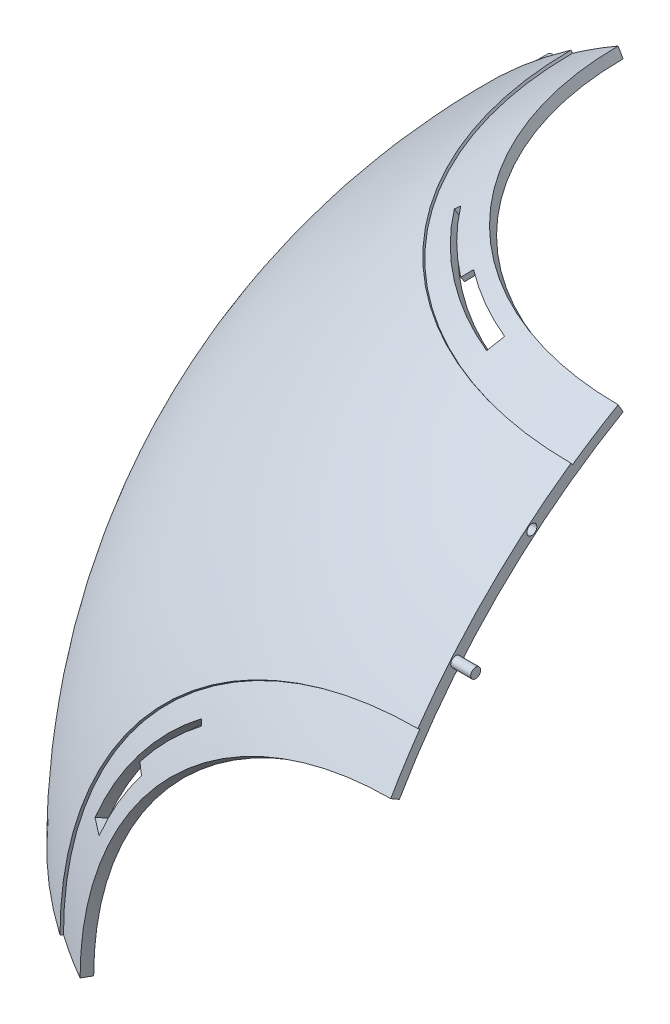
SolidWorks part; units mm, degrees
ref_plane "Front Plane" through (0, 0, 0) normal (0, 0, 1) x (1, 0, 0)
ref_plane "Top Plane" through (0, 0, 0) normal (0, 1, 0) x (1, 0, 0)
ref_plane "Right Plane" through (0, 0, 0) normal (1, 0, 0) x (0, 0, -1)
sketch "Sketch1" plane through (0, 0, 0) normal (0, 0, 1) x (1, 0, 0)
  line L0 (0, 0) -> (0, 282.4311)
  line L1 (-122.5, 212.1762) -> (-124.5, 215.6403)
  line L2 (-142.8205, 203.9689) -> (-143.3941, 204.788)
  line L3 (-245, 0) -> (-250, 0)
  arc A0 (-143.3941, 204.788) -> (-250, 0) centre (0, 0) ccw
  arc A1 (-124.5, 215.6403) -> (-142.8205, 203.9689) centre (0, 0) ccw
  arc A2 (-122.5, 212.1762) -> (-245, 0) centre (0, 0) ccw
  dimension "D1" = 500
  dimension "D2" = 498
  dimension "D3" = 490
  dimension "D4" = 5
  dimension "D5" = 30
revolve "Revolve1" add sketch "Sketch1" angle 90 about L0 region at (-214.3457, 123.7526, 0)
sketch "Sketch2" plane through (0, 0, 0) normal (1, 0, 0) x (0, 0, -1)
  line L0 (0, 0) -> (-288.7114, 0)
  line L1 (-212.1762, 122.5) -> (-215.6403, 124.5)
  line L2 (-203.9689, 142.8205) -> (-204.788, 143.3941)
  arc A0 (-204.788, 143.3941) -> (-250, 0) centre (0, 0) ccw
  arc A1 (-212.1762, 122.5) -> (-245, 0) centre (0, 0) ccw
  arc A2 (-203.9689, 142.8205) -> (-215.6403, 124.5) centre (0, 0) ccw
  dimension "D1" = 498
  dimension "D2" = 490
  dimension "D3" = 5
  dimension "D4" = 30
revolve "Cut-Revolve2" cut sketch "Sketch2" angle 360 about L0 region at (0, 1.506, 247.5)
sketch "Sketch3" plane through (0, 0, 0) normal (0, 0, -1) x (-1, 0, 0)
  line L0 (0, 0) -> (307.3195, 0)
  line L1 (203.9689, 142.8205) -> (204.788, 143.3941)
  line L2 (0, 0) -> (215.6403, 124.5)
  arc A0 (245, 0) -> (212.1762, 122.5) centre (0, 0) ccw
  arc A1 (250, 0) -> (204.788, 143.3941) centre (0, 0) ccw
  arc A2 (215.6403, 124.5) -> (203.9689, 142.8205) centre (0, 0) ccw
  dimension "D1" = 498
  dimension "D2" = 30
  dimension "D3" = 5
revolve "Cut-Revolve3" cut sketch "Sketch3" angle 360 about L0 region at (-238.1065, 63.8005, 0)
sketch "Sketch4" plane through (0, 0, 0) normal (0, 0, -1) x (-1, 0, 0)
  line L0 (0, 0) -> (143.3941, 204.788)
  circle A0 centre (0, 0) radius 247.5
  circle A1 centre (159.0899, 189.596) radius 2
  circle A2 centre (189.596, 159.0899) radius 2.025
  dimension "D1" = 495
  dimension "D2" = 4.05
  dimension "D5" = 4
  dimension "D3" = 10
  dimension "D4" = 5
extrude "Boss-Extrude1" add sketch "Sketch4" along normal blind 8 contours A0 A1 | A0 A1 region at (-159.6346, 190.2451, 0) region at (-158.5434, 188.9446, 0)
extrude "Cut-Extrude2" cut sketch "Sketch4<4>" against normal blind 8 contours A0 A2 | A0 A2 region at (-188.9365, 158.5365, 0) region at (-190.2532, 159.6414, 0)
sketch "Sketch4<4>" plane through (0, 0, 0) normal (0, 0, -1) x (-1, 0, 0) same geometry as "Sketch4"
sketch "Sketch5" plane through (0, 0, 0) normal (1, 0, 0) x (0, 0, -1)
  line L0 (0, 0) -> (-143.3941, 204.788)
  circle A0 centre (0, 0) radius 247.5
  circle A1 centre (-159.0899, 189.596) radius 2.025
  circle A2 centre (-189.596, 159.0899) radius 2
  dimension "D1" = 4
  dimension "D2" = 4.05
  dimension "D5" = 10
  dimension "D3" = 495
  dimension "D4" = 5
extrude "Boss-Extrude2" add sketch "Sketch5" along normal blind 8 contours A0 A2 | A0 A2 region at (0, 159.6346, 190.2451) region at (0, 158.5434, 188.9446)
extrude "Cut-Extrude3" cut sketch "Sketch5<3>" against normal blind 8 contours A0 A1 | A0 A1 region at (0, 188.9365, 158.5365) region at (0, 190.2532, 159.6414)
sketch "Sketch5<3>" plane through (0, 0, 0) normal (1, 0, 0) x (0, 0, -1) same geometry as "Sketch5"
sketch "Sketch6" plane through (0, 0, 0) normal (0, -1, 0) x (1, 0, 0)
  line L0 (0, 0) -> (-143.3941, 204.788)
  circle A0 centre (0, 0) radius 247.5
  circle A1 centre (-189.596, 159.0899) radius 2
  circle A2 centre (-159.0899, 189.596) radius 2.025
  dimension "D1" = 495
  dimension "D2" = 4.05
  dimension "D3" = 4
  dimension "D4" = 5
  dimension "D5" = 10
extrude "Cut-Extrude4" cut sketch "Sketch6" against normal blind 8 contours A0 A2 | A0 A2 region at (-158.5365, 0, 188.9365) region at (-159.6414, 0, 190.2532)
extrude "Boss-Extrude3" add sketch "Sketch6<4>" along normal blind 8 contours A0 A1 | A0 A1 region at (-190.2451, 0, 159.6346) region at (-188.9446, 0, 158.5434)
sketch "Sketch6<4>" plane through (0, 0, 0) normal (0, -1, 0) x (1, 0, 0) same geometry as "Sketch6"
sketch "Sketch10" plane through (0, 0, 0) normal (0, 0, 1) x (1, 0, 0)
  line L0 (0, 0) -> (-235.3166, 0)
  line L1 (0, 0) -> (-214.7234, 214.7234)
  dimension "D1" = 45
ref_plane "Plane1" through (0, 0, 0) normal (0, -0.3827, 0.9239) x (-1, 0, 0)
sketch "Sketch11" plane through (0, 0, 0) normal (0, -0.3827, 0.9239) x (-1, 0, 0)
  line L0 (0, 0) -> (212.3074, -130.1021)
  line L1 (0, 0) -> (208.829, -135.6151)
  line L2 (0, 0) -> (204.788, -143.3941)
  line L3 (0, 0) -> (271.2872, 0)
  circle A0 centre (0, 0) radius 249
  circle A1 centre (0, 0) radius 245
  dimension "D1" = 498
  dimension "D2" = 490
  dimension "D3" = 1.5
  dimension "D4" = 2
revolve "Cut-Revolve4" cut sketch "Sketch11" angle 15 about L0 region at (-208.8934, 121.7691, 50.4384) reverse direction yes
sketch "Sketch12" plane through (0, 0, 0) normal (0, 0.6088, -0.7934) x (1, 0, 0)
  line L0 (0, 0) -> (-210.0045, -133.7876)
  line L1 (0, 0) -> (-208.829, -135.6151)
  line L2 (0, 0) -> (-204.788, -143.3941)
  line L3 (0, 0) -> (-212.3074, -130.1021)
  circle A0 centre (0, 0) radius 249
  circle A1 centre (0, 0) radius 245
  circle A2 centre (0, 0) radius 247
  dimension "D1" = 490
  dimension "D4" = 494
  dimension "D2" = 2
  dimension "D3" = 0.5
revolve "Cut-Revolve5" cut sketch "Sketch12" angle 15 about L0 region at (-206.8961, 105.5795, 81.014) region at (-208.6183, 103.4209, 79.3577) region at (-208.5781, 106.4378, 81.6726) reverse direction yes
ref_plane "Plane2" through (0, 0, 0) normal (0, -0.7071, 0.7071) x (-1, 0, 0)
sketch "Sketch15" plane through (0, 0, 0) normal (0, 1, 0) x (1, 0, 0)
  line L1 (0, 0) -> (-189.3752, -189.3752)
  line L2 (0, 0) -> (0, -178.2847)
  dimension "D1" = 45
ref_plane "Plane3" through (0, 0, 0) normal (-0.7071, 0, -0.7071) x (-0.7071, 0, 0.7071)
ref_axis "Axis1" through (9.4688, -9.4688, -9.4688) along (-0.5774, 0.5774, 0.5774)
pattern_circular "CirPattern5" count 3 every 120 about axis through (9.4688, -9.4688, -9.4688) along (-0.5774, 0.5774, 0.5774) of "Cut-Revolve4", "Cut-Revolve5"
